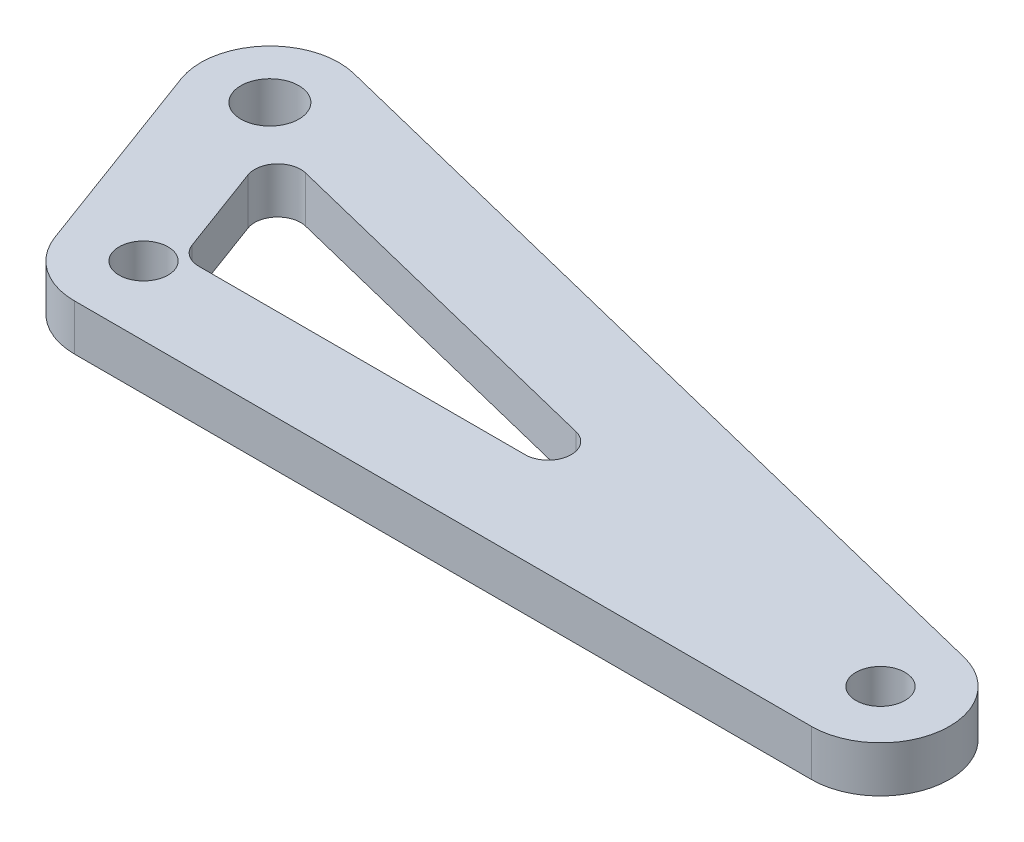
SolidWorks part; units mm, degrees
ref_plane "Front Plane" through (0, 0, 0) normal (0, 0, 1) x (1, 0, 0)
ref_plane "Top Plane" through (0, 0, 0) normal (0, 1, 0) x (1, 0, 0)
ref_plane "Right Plane" through (0, 0, 0) normal (1, 0, 0) x (0, 0, -1)
sketch "Sketch1" plane through (0, 0, 0) normal (0, 1, 0) x (1, 0, 0)
  line L0 (0, 0) -> (101.5644, 0) construction
  line L1 (101.5644, 0) -> (-10.2264, 27.6351) construction
  line L2 (-10.2264, 27.6351) -> (0, 0) construction
  line L3 (-23.321, 35.5752) -> (-7.3987, -7.4519)
  line L4 (-4.421, -9.525) -> (153.7124, -9.525)
  line L5 (154.4744, -3.2678) -> (-19.5814, 39.7594)
  line L6 (0.6524, 21.6752) -> (50.1784, 9.4322)
  line L7 (49.4165, 3.175) -> (4.421, 3.175)
  line L8 (1.4433, 5.2481) -> (-3.0872, 17.4911)
  circle A0 centre (0, 0) radius 3.3782
  circle A1 centre (-10.2264, 27.6351) radius 4
  circle A2 centre (101.5644, 0) radius 3.3782
  arc A3 (50.1784, 9.4322) -> (49.4165, 3.175) centre (49.4165, 6.35) cw
  arc A4 (4.421, 3.175) -> (1.4433, 5.2481) centre (4.421, 6.35) cw
  arc A5 (0.6524, 21.6752) -> (-3.0872, 17.4911) centre (-0.1096, 18.593) ccw
  arc A6 (154.4744, -3.2678) -> (153.7124, -9.525) centre (153.7124, -6.35) cw
  arc A7 (-4.421, -9.525) -> (-7.3987, -7.4519) centre (-4.421, -6.35) cw
  arc A8 (-19.5814, 39.7594) -> (-23.321, 35.5752) centre (-20.3433, 36.6771) ccw
  circle A9 centre (101.5644, 0) radius 9.525
  circle A10 centre (0, 0) radius 9.525
  circle A11 centre (-10.2264, 27.6351) radius 9.525
  point P18 (-0.8219, 11.3696)
  dimension "D4" = 6.7564
  dimension "D5" = 8
  dimension "D6" = 9.525
  dimension "D12" = 3.175
  dimension "D2" = 29.4665
  dimension "D3" = 115.156
  dimension "D7" = 9.525
  dimension "D8" = 9.525
  dimension "D9" = 12.7
  dimension "D10" = 12.7
  dimension "D11" = 12.7
  dimension "D13" = 101.5644
extrude "Boss-Extrude2" add sketch "Sketch1" along normal blind 6.35 contours A11 L3 A10 L8 A5 L6 A3 L7 L4 A9 L5 | A10 L7 A4 L8 A0 | A9 A2 | A11 A1 region at (-8.3155, 0, -16.9651) region at (-17.1274, 0, -33.8029) region at (-7.6343, 0, -5.2329) region at (108.8522, 0, -5.7056)
